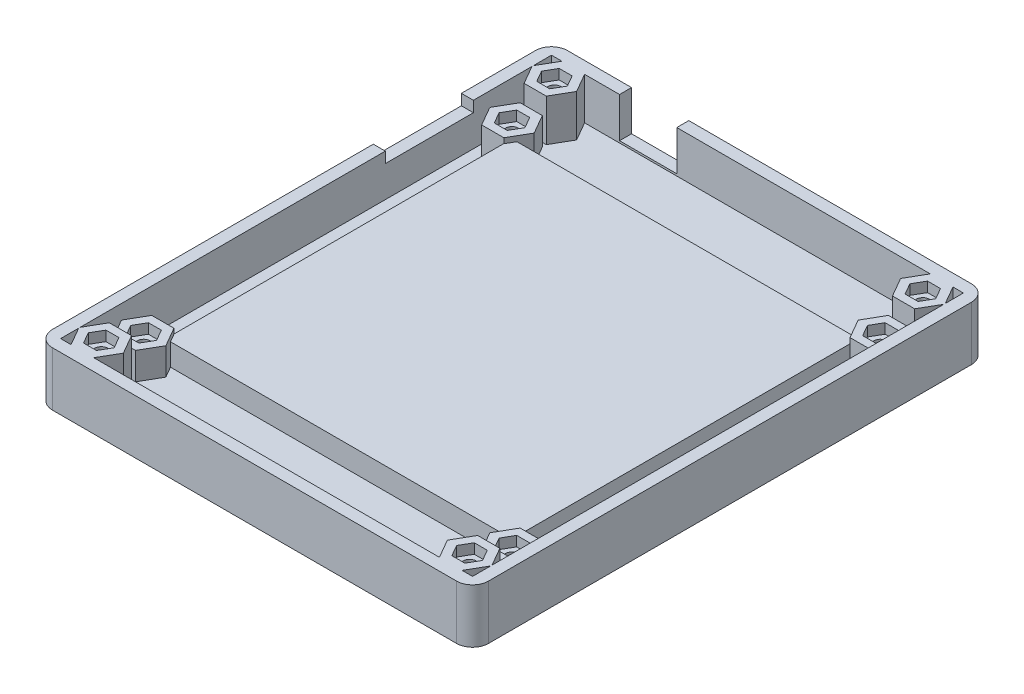
SolidWorks part; units mm, degrees
ref_plane "Přední rovina" through (0, 0, 0) normal (0, 0, 1) x (1, 0, 0)
ref_plane "Horní rovina" through (0, 0, 0) normal (0, 1, 0) x (1, 0, 0)
ref_plane "Pravá rovina" through (0, 0, 0) normal (1, 0, 0) x (0, 0, -1)
sketch "Skica1" plane through (0, 0, 0) normal (0, 1, 0) x (1, 0, 0)
  line L0 (0, 0) -> (-100, 100) construction
  line L1 (-50, 50) -> (50, 50) construction
  line L2 (-50, 50) -> (-50, -50) construction
  line L3 (-50, -50) -> (50, -50) construction
  line L4 (50, 50) -> (50, -50) construction
  line L5 (-50, 50) -> (50, -50) construction
  line L6 (-50, -50) -> (50, 50) construction
  line L7 (-47.6166, 43.2) -> (-44.3834, 43.2)
  line L8 (-44.3834, 43.2) -> (-42.7668, 46)
  line L9 (-42.7668, 46) -> (-44.3834, 48.8)
  line L10 (-44.3834, 48.8) -> (-47.6166, 48.8)
  line L11 (-47.6166, 48.8) -> (-49.2332, 46)
  line L12 (-49.2332, 46) -> (-47.6166, 43.2)
  line L13 (-48.7713, 41.2) -> (-43.2287, 41.2)
  line L14 (-43.2287, 41.2) -> (-40.4574, 46)
  line L15 (-40.4574, 46) -> (-43.2287, 50.8)
  line L16 (-43.2287, 50.8) -> (-48.7713, 50.8)
  line L17 (-48.7713, 50.8) -> (-51.5426, 46)
  line L18 (-51.5426, 46) -> (-48.7713, 41.2)
  line L19 (0, 81.3987) -> (0, -91.9033) construction
  line L20 (-42.7668, 56.6) -> (-44.3834, 59.4)
  line L21 (-44.3834, 59.4) -> (-47.6166, 59.4)
  line L22 (-47.6166, 59.4) -> (-49.2332, 56.6)
  line L23 (-49.2332, 56.6) -> (-47.6166, 53.8)
  line L24 (-47.6166, 53.8) -> (-44.3834, 53.8)
  line L25 (-44.3834, 53.8) -> (-42.7668, 56.6)
  line L26 (-48.7713, 51.8) -> (-43.2287, 51.8)
  line L27 (-43.2287, 51.8) -> (-40.4574, 56.6)
  line L28 (-40.4574, 56.6) -> (-43.2287, 61.4)
  line L29 (-43.2287, 61.4) -> (-48.7713, 61.4)
  line L30 (-48.7713, 61.4) -> (-51.5426, 56.6)
  line L31 (-51.5426, 56.6) -> (-48.7713, 51.8)
  line L36 (74.9355, -74.9355) -> (-74.9355, 74.9355) construction
  line L37 (74.9355, 74.9355) -> (-74.9355, -74.9355) construction
  line L38 (-54.4426, -64.3) -> (54.4426, -64.3)
  line L39 (-54.4426, -64.3) -> (-54.4426, 64.3)
  line L40 (-54.4426, 64.3) -> (54.4426, 64.3)
  line L41 (54.4426, -64.3) -> (54.4426, 64.3)
  line L42 (-54.4426, -64.3) -> (54.4426, 64.3) construction
  line L43 (-54.4426, 64.3) -> (54.4426, -64.3) construction
  line L44 (-106.951, 0) -> (125.2961, 0) construction
  line L45 (-46, 37.8836) -> (-46, 68.4593) construction
  line L47 (-51.4426, -61.3) -> (51.4426, -61.3)
  line L48 (-51.4426, -61.3) -> (-51.4426, 61.3)
  line L49 (-51.4426, 61.3) -> (51.4426, 61.3)
  line L50 (51.4426, -61.3) -> (51.4426, 61.3)
  line L51 (-51.4426, -61.3) -> (51.4426, 61.3) construction
  line L52 (-51.4426, 61.3) -> (51.4426, -61.3) construction
  circle A0 centre (-46, 46) radius 2.8 construction
  circle A1 centre (-46, 46) radius 4.8 construction
  circle A2 centre (-46, 56.6) radius 2.8 construction
  circle A3 centre (-46, 56.6) radius 4.8 construction
  circle A4 centre (-46, 46) radius 1.6
  circle A5 centre (-46, 56.6) radius 1.6
  point P0 (0, 0)
  point P7 (-41.8431, 43.6)
  point P52 (-48.8, 54.9834)
  point P53 (-46, 53.3668)
  point P54 (-49.088, 57.5579)
  dimension "D9" = 3
  dimension "D10" = 3
  dimension "D11" = 0.1
  dimension "D12" = 0.1
  dimension "D13" = 3.2
  dimension "D14" = 3.2
  dimension "D1" = 100
  dimension "D2" = 100
  dimension "D3" = 5.6
  dimension "D4" = 4
  dimension "D5" = 9.6
  dimension "D6" = 5.6
  dimension "D7" = 9.6
  dimension "D8" = 1
extrude "Přidat vysunutím25" add sketch "Skica1" against normal blind 3 contours L49 L48 L30 | L20 L21 L22 L23 L24 L25 | L7 L8 L9 L10 L11 L12 | L48 L47 L50 L49 | L13 L14 L15 L16 L17 L18 | L26 L27 L28 L29 L30 L31 region at (-50.5714, 0, -59.7911)
extrude "Přidat vysunutím26" add sketch "Skica1<21>" against normal blind 3 and the other way blind 10.5 contours L38 L41 L40 L39 L50 L47 L48 L18 L17 L31 L30 L49 L29 L28 | L18 L48 L17 | L31 L48 L30 | L30 L49 L28 L29 region at (-51.4759, 0, -46) region at (-51.4759, 0, -56.6) region at (-46, 0, -61.3498) region at (-52.7575, 0, 0)
sketch "Skica1<21>" plane through (0, 0, 0) normal (0, 1, 0) x (1, 0, 0) same geometry as "Skica1"
extrude "Přidat vysunutím28" add sketch "Skica1<23>" along normal blind 6.8 contours L48 L18 L13 L14 L15 L16 L17 L12 L11 L10 L9 L8 L7 | L18 L48 L17 region at (-49.9806, 0, -43.5863) region at (-51.4759, 0, -46)
sketch "Skica1<23>" plane through (0, 0, 0) normal (0, 1, 0) x (1, 0, 0) same geometry as "Skica1"
extrude "Přidat vysunutím29" add sketch "Skica1<24>" along normal blind 4.3 contours L11 L12 L7 L8 L9 L10 region at (-48.3508, 0, -44.6428)
sketch "Skica1<24>" plane through (0, 0, 0) normal (0, 1, 0) x (1, 0, 0) same geometry as "Skica1"
pattern_linear "LinPole3" count 2 spacing 92 along (1, 0, 0) count 2 spacing 92 along (0, 0, 1) of "Přidat vysunutím28", "Přidat vysunutím29"
extrude "Přidat vysunutím30" add sketch "Skica1<25>" along normal blind 10.5 contours L49 L30 L48 L31 L26 L27 L28 L25 L24 L23 L22 L21 L20 | L30 L49 L28 L29 | L31 L48 L30 region at (-51.2973, 0, -56.6) region at (-51.4759, 0, -56.6) region at (-46, 0, -61.3498)
sketch "Skica1<25>" plane through (0, 0, 0) normal (0, 1, 0) x (1, 0, 0) same geometry as "Skica1"
extrude "Přidat vysunutím31" add sketch "Skica1<26>" along normal blind 8 contours L24 L25 L20 L21 L22 L23 A5 region at (-43.6492, 0, -55.2428)
sketch "Skica1<26>" plane through (0, 0, 0) normal (0, 1, 0) x (1, 0, 0) same geometry as "Skica1"
pattern_linear "LinPole4" count 2 spacing 92 along (1, 0, 0) count 2 spacing 113.2 along (0, 0, 1) of "Přidat vysunutím31", "Přidat vysunutím30"
sketch "Skica8" plane through (0, 0, 0) normal (0, 1, 0) x (1, 0, 0)
  line L1 (-43.2691, -43.2691) -> (43.2691, -43.2691)
  line L2 (-43.2691, -43.2691) -> (-43.2691, 43.2691)
  line L3 (-43.2691, 43.2691) -> (43.2691, 43.2691)
  line L4 (43.2691, -43.2691) -> (43.2691, 43.2691)
  line L5 (-43.2691, -43.2691) -> (43.2691, 43.2691) construction
  line L6 (-43.2691, 43.2691) -> (43.2691, -43.2691) construction
  point P0 (0, 0)
  dimension "D1" = 86.5383
extrude "Přidat vysunutím32" add sketch "Skica8" along normal blind 5.5
fillet "Zaoblit4" radius 4 4 edges at (-54.4426, 3.75, 64.3) (54.4426, 3.75, 64.3) (54.4426, 3.75, -64.3) (-54.4426, 3.75, -64.3)
sketch "Skica9" plane through (-54.4426, 0, 0) normal (-1, 0, 0) x (0, 0, 1)
  line L0 (60.3, 10.5) -> (-60.3, 10.5) construction
  line L1 (-19.8, 7.8) -> (-41.8, 7.8)
  line L2 (-19.8, 7.8) -> (-19.8, 10.5)
  line L3 (-19.8, 10.5) -> (-41.8, 10.5)
  line L4 (-41.8, 7.8) -> (-41.8, 10.5)
  line L5 (-19.8, 7.8) -> (-41.8, 10.5) construction
  line L6 (-19.8, 10.5) -> (-41.8, 7.8) construction
  line L7 (-64.3, -3) -> (-64.3, 10.5) construction
  point P0 (-30.8, 9.15)
  dimension "D1" = 22
  dimension "D2" = 22.5
  dimension "D3" = 2.7
extrude "Odebrat vysunutím1" cut sketch "Skica9" against normal blind 10 contours L4 L3 L2 L1
sketch "Skica10" plane through (0, 0, -64.3) normal (0, 0, -1) x (-1, 0, 0)
  line L0 (50.4426, 10.5) -> (-50.4426, 10.5) construction
  line L1 (20.1426, 0.5) -> (34.4426, 0.5)
  line L2 (20.1426, 0.5) -> (20.1426, 10.5)
  line L3 (20.1426, 10.5) -> (34.4426, 10.5)
  line L4 (34.4426, 0.5) -> (34.4426, 10.5)
  line L5 (54.4426, 10.5) -> (54.4426, -3) construction
  dimension "D1" = 10
  dimension "D2" = 14.3
  dimension "D3" = 20
extrude "Odebrat vysunutím2" cut sketch "Skica10" against normal blind 5
